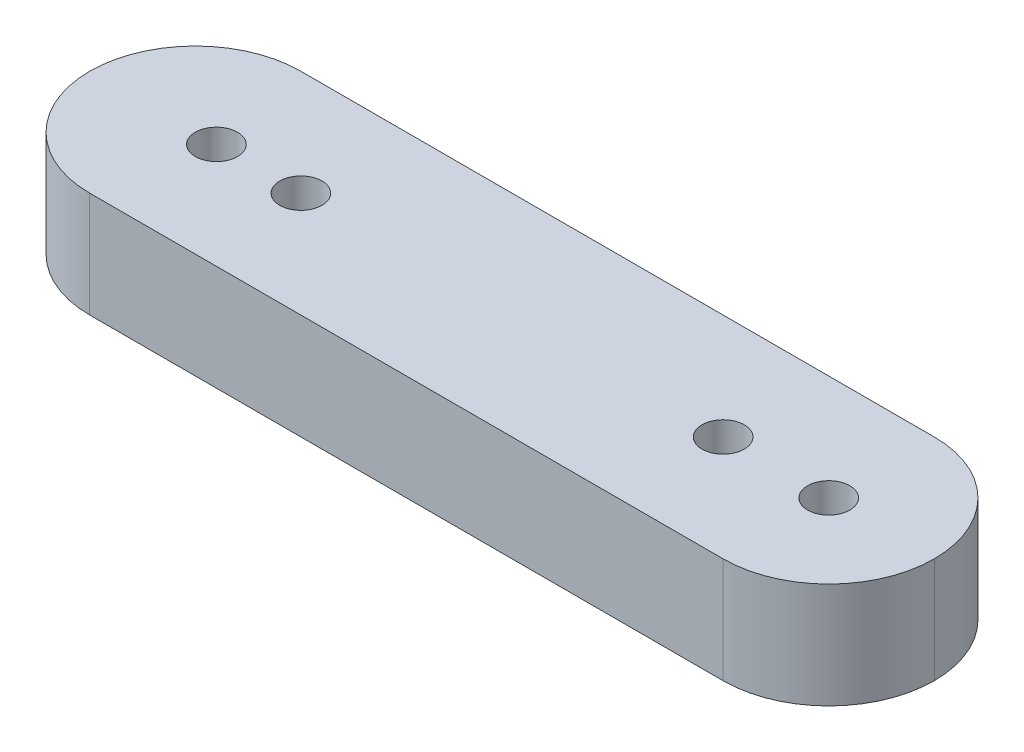
SolidWorks part; units mm, degrees
ref_plane "Front Plane" through (0, 0, 0) normal (0, 0, 1) x (1, 0, 0)
ref_plane "Top Plane" through (0, 0, 0) normal (0, 1, 0) x (1, 0, 0)
ref_plane "Right Plane" through (0, 0, 0) normal (1, 0, 0) x (0, 0, -1)
sketch "Sketch1" plane through (0, 0, 0) normal (0, 1, 0) x (1, 0, 0)
  line L1 (-20, -5) -> (20, -5)
  line L2 (-20, -5) -> (-20, 5)
  line L3 (-20, 5) -> (20, 5)
  line L4 (20, -5) -> (20, 5)
  line L5 (-20, -5) -> (20, 5) construction
  line L6 (-20, 5) -> (20, -5) construction
  point P0 (0, 0)
  point P6 (0, 5)
  dimension "D1" = 40
  dimension "D2" = 10
extrude "Boss-Extrude1" add sketch "Sketch1" along normal blind 5
sketch "Sketch2" plane through (0, 0, 0) normal (0, 1, 0) x (1, 0, 0)
  line L0 (-20, 0) -> (20, 0) construction
  line L1 (-20, 5) -> (-20, -5) construction
  line L2 (20, -5) -> (20, 5) construction
  circle A0 centre (10, 0) radius 1
  circle A1 centre (15, 0) radius 1
  circle A2 centre (-10, 0) radius 1
  circle A3 centre (-14, 0) radius 1
  dimension "D5" = 2
  dimension "D6" = 2
  dimension "D7" = 2
  dimension "D8" = 2
  dimension "D1" = 10
  dimension "D2" = 4
  dimension "D3" = 10
  dimension "D4" = 5
extrude "Cut-Extrude1" cut sketch "Sketch2" along normal blind 5
fillet "Fillet1" radius 5 4 edges at (20, 2.5, -5) (-20, 2.5, -5) (20, 2.5, 5) (-20, 2.5, 5)
